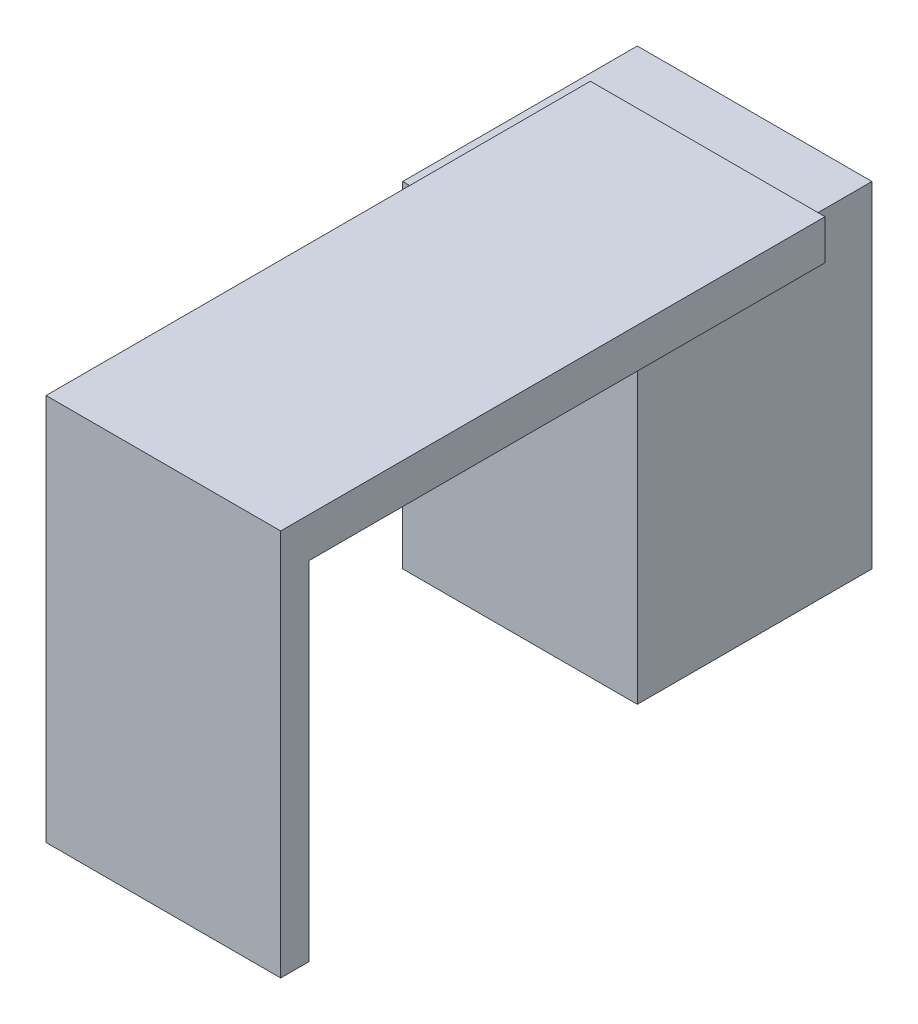
SolidWorks part; units mm, degrees
note: The reader was unsure of these and kept them because the rebuilt part matched: shared geometry of "Sketch3<3>".
ref_plane "Front Plane" through (0, 0, 0) normal (0, 0, 1) x (1, 0, 0)
ref_plane "Top Plane" through (0, 0, 0) normal (0, 1, 0) x (1, 0, 0)
ref_plane "Right Plane" through (0, 0, 0) normal (1, 0, 0) x (0, 0, -1)
sketch "Sketch2" plane through (0, 0, 0) normal (1, 0, 0) x (0, 0, -1)
  line L0 (0, 0) -> (0, 800)
  line L1 (0, 800) -> (1160, 800)
  line L2 (1160, 800) -> (1160, 740)
  line L3 (1160, 740) -> (60, 740)
  line L4 (60, 740) -> (60, 0)
  line L5 (60, 0) -> (0, 0)
  dimension "D1" = 800
  dimension "D2" = 1160
  dimension "D3" = 60
  dimension "D4" = 60
extrude "Boss-Extrude1" add sketch "Sketch2" along normal mid plane 500 contours L4 L5 L0 L1 L2 L3
sketch "Sketch3" plane through (0, 0, 0) normal (0, 1, 0) x (1, 0, 0)
  line L0 (-250, 0) -> (-250, 1160) construction
  line L1 (-350, 1360) -> (150, 1360)
  line L2 (-350, 1360) -> (-350, 860)
  line L3 (-350, 860) -> (150, 860)
  line L4 (150, 1360) -> (150, 860)
  line L5 (-100, 860) -> (-100, 1360) construction
  line L6 (-350, 1110) -> (250, 1110) construction
  line L7 (250, 1160) -> (-250, 1160) construction
  line L9 (-325, 1335) -> (-325, 885)
  line L10 (-325, 885) -> (125, 885)
  line L11 (125, 1335) -> (125, 885)
  line L12 (-325, 1335) -> (125, 1335)
  point P8 (-50, 1060)
  point P232 (-100, 1110)
  dimension "D1" = 100
  dimension "D2" = 200
  dimension "D3" = 500
  dimension "D4" = 25
extrude "Boss-Extrude2" add sketch "Sketch3" along normal up to surface (740 mm away) contours L12 L9 L10 L11 up to face at (0, 740, -610)
extrude "Boss-Extrude3" add sketch "Sketch3<3>" along normal up to surface (715 mm away) from offset 25 contours L4 L1 L2 L3 L9 L12 L11 L10 up to face at (41.6667, 740, -701.6667)
sketch "Sketch3<3>" plane through (0, 0, 0) normal (0, 1, 0) x (1, 0, 0) same geometry as "Sketch3"
sketch "Sketch4" plane through (0, 800, 0) normal (0, 1, 0) x (1, 0, 0)
  line L4 (-250, 1160) -> (-250, 0)
  line L5 (-250, 0) -> (250, 0)
  line L6 (250, 0) -> (250, 1160)
  line L7 (250, 1160) -> (-250, 1160)
  line L8 (-250, 1160) -> (-250, 0)
  line L9 (-250, 0) -> (250, 0)
  line L10 (250, 0) -> (250, 1160)
  line L11 (250, 1160) -> (-250, 1160)
  dimension "D1" = 0
extrude "Boss-Extrude4" add sketch "Sketch4" along normal blind 25 contours L8 L9 L10 L11
equation "\"S\" = 60"
equation "\"D3@Sketch2\"=\"S\""
equation "\"D4@Sketch2\"=\"S\""
equation "\"H\"=25"
equation "\"D19@Boss-Extrude3\"=\"H\""
equation "\"D1@Boss-Extrude4\"=\"H\""
